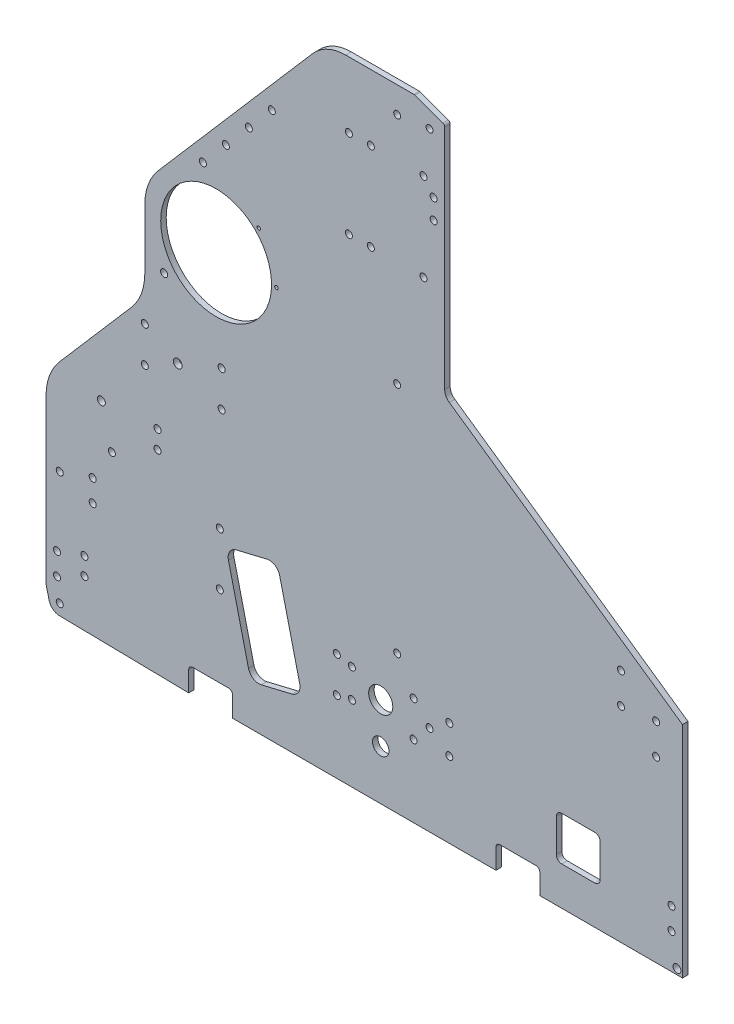
SolidWorks part; units mm, degrees
ref_plane "Front Plane" through (0, 0, 0) normal (0, 0, 1) x (1, 0, 0)
ref_plane "Top Plane" through (0, 0, 0) normal (0, 1, 0) x (1, 0, 0)
ref_plane "Right Plane" through (0, 0, 0) normal (1, 0, 0) x (0, 0, -1)
sketch "Sketch1" plane through (0, 0, 0) normal (0, 0, 1) x (1, 0, 0)
  line L0 (82.55, -20.32) -> (82.55, -6.35)
  line L2 (0, 0) -> (0, 157.48)
  line L4 (368.3, -20.32) -> (368.3, 106.68)
  line L5 (82.55, -6.35) -> (107.95, -6.35)
  line L6 (107.95, -6.35) -> (107.95, -20.32)
  line L7 (107.95, -20.32) -> (260.35, -20.32)
  line L8 (260.35, -20.32) -> (260.35, -6.35)
  line L9 (260.35, -6.35) -> (285.75, -6.35)
  line L10 (285.75, -6.35) -> (285.75, -20.32)
  line L11 (285.75, -20.32) -> (368.3, -20.32)
  line L12 (361.95, 12.7) -> (368.3, 12.7) construction
  line L13 (0, 0) -> (6.35, 0) construction
  line L14 (0.1896, -7.8901) -> (1.7771, -14.2401)
  line L15 (7.8295, -19.0491) -> (82.55, -20.32)
  line L16 (0, 0) -> (0, -6.35)
  line L17 (76.2, 141.605) -> (79.375, 141.605) construction
  line L18 (57.15, 131.2863) -> (101.6, 131.2862) construction
  line L19 (57.15, 131.2863) -> (57.15, 151.9238) construction
  line L20 (101.6, 131.2862) -> (101.6, 151.9237) construction
  line L21 (57.15, 151.9238) -> (101.6, 151.9237) construction
  line L22 (57.15, 131.2863) -> (101.6, 151.9237) construction
  line L23 (101.6, 131.2862) -> (57.15, 151.9238) construction
  line L25 (203.2, 59.805) -> (203.2, 194.805) construction
  line L26 (203.2, 194.805) -> (203.2, 329.805) construction
  line L27 (355.6, 332.105) -> (330.2, 332.105) construction
  line L28 (330.2, 332.105) -> (330.2, 217.805) construction
  line L29 (330.2, 217.805) -> (355.6, 217.805) construction
  line L30 (355.6, 217.805) -> (355.6, 332.105) construction
  line L31 (203.2, 344.805) -> (203.2, 194.805) construction
  line L32 (50.8, 332.105) -> (76.2, 332.105) construction
  line L33 (76.2, 332.105) -> (76.2, 217.805) construction
  line L34 (50.8, 217.805) -> (50.8, 332.105) construction
  line L35 (76.2, 217.805) -> (50.8, 217.805) construction
  line L36 (213.2, 344.805) -> (230.6638, 338.455)
  line L37 (203.2, 344.805) -> (161.925, 344.805)
  line L38 (203.2, 344.805) -> (213.2, 344.805)
  line L39 (348.5362, 344.805) -> (413.4623, 344.805)
  line L40 (348.5362, 344.805) -> (230.6638, 344.805) construction
  line L42 (161.925, 344.805) -> (0, 157.48)
  line L44 (230.6638, 338.455) -> (230.6638, 202.565)
  line L45 (230.6638, 202.565) -> (368.3, 106.68)
  line L46 (213.2, 344.805) -> (-141.0713, 344.805) construction
  circle A0 centre (6.35, 0) radius 2.032
  circle A1 centre (6.35, 12.7) radius 2.032
  circle A2 centre (361.95, 0) radius 2.032
  circle A3 centre (361.95, 12.7) radius 2.032
  arc A5 (1.7771, -14.2401) -> (7.8295, -19.0491) centre (7.9375, -12.7) ccw
  circle A6 centre (7.9375, -12.7) radius 2.032
  arc A7 (0, -6.35) -> (0.1896, -7.8901) centre (6.35, -6.35) ccw
  circle A8 centre (38.1, 78.105) radius 2.032
  circle A9 centre (76.2, 141.605) radius 2.54
  circle A10 centre (101.6, 131.2862) radius 2.032
  circle A11 centre (101.6, 151.9237) radius 2.032
  circle A12 centre (57.15, 151.9238) radius 2.032
  circle A13 centre (57.15, 131.2863) radius 2.032
  circle A15 centre (203.2, 59.805) radius 2
  circle A16 centre (203.2, 194.805) radius 2
  circle A17 centre (203.2, 329.805) radius 2
  circle A18 centre (63.5, 313.055) radius 2.032
  circle A20 centre (355.6, 332.105) radius 2.032
  circle A21 centre (330.2, 332.105) radius 2.032
  circle A22 centre (355.6, 217.805) radius 2.032
  circle A23 centre (330.2, 217.805) radius 2.032
  circle A24 centre (50.8, 332.105) radius 2.032
  circle A25 centre (76.2, 332.105) radius 2.032
  circle A26 centre (50.8, 217.805) radius 2.032
  circle A27 centre (76.2, 217.805) radius 2.032
  circle A28 centre (221.9319, 332.105) radius 2
  circle A29 centre (224.3138, 298.831) radius 2.032
  circle A30 centre (353.06, 100.7351) radius 2.032
  circle A31 centre (332.74, 115.9751) radius 2.032
  circle A32 centre (332.74, 98.1951) radius 2.032
  circle A33 centre (353.06, 82.9551) radius 2.032
  circle A34 centre (117.3562, 280.4276) radius 2.032
  circle A35 centre (104.0678, 265.0548) radius 2.032
  circle A36 centre (90.7795, 249.682) radius 2.032
  circle A38 centre (130.6445, 295.8004) radius 2.032
  circle A39 centre (68.326, 182.9237) radius 2.032
  circle A40 centre (224.3138, 287.401) radius 2.032
  point P82 (203.2, 344.805)
  point P83 (221.9319, 341.63)
  point P90 (368.3, 62.484)
  dimension "D6" = 4.064
  dimension "D10" = 6.35
  dimension "D11" = 4.064
  dimension "D17" = 38.1
  dimension "D27" = 4
  dimension "D31" = 4.064
  dimension "D32" = 41.275
  dimension "D36" = 4.064
  dimension "D47" = 39.624
  dimension "D48" = 4.064
  dimension "D25" = 5.08
  dimension "D26" = 4.064
  dimension "D52" = 4.064
  dimension "D65" = 4.064
  dimension "D2" = 127
  dimension "D3" = 13.97
  dimension "D4" = 25.4
  dimension "D5" = 152.4
  dimension "D7" = 12.7
  dimension "D8" = 6.35
  dimension "D9" = 20.32
  dimension "D12" = 12.7
  dimension "D13" = 1.5875
  dimension "D14" = 82.55
  dimension "D15" = 368.3
  dimension "D16" = 6.35
  dimension "D18" = 98.425
  dimension "D19" = 38.1
  dimension "D20" = 63.5
  dimension "D21" = 3.175
  dimension "D22" = 270
  dimension "D23" = 20.6375
  dimension "D24" = 44.45
  dimension "D28" = 135
  dimension "D29" = 12.7
  dimension "D30" = 15
  dimension "D33" = 63.5
  dimension "D34" = 27.4638
  dimension "D35" = 12.7
  dimension "D37" = 114.3
  dimension "D38" = 25.4
  dimension "D39" = 12.7
  dimension "D40" = 157.48
  dimension "D41" = 142.24
  dimension "D42" = 365.125
  dimension "D43" = 10
  dimension "D44" = 6.35
  dimension "D45" = 31.75
  dimension "D46" = 6.35
  dimension "D49" = 6.35
  dimension "D50" = 203.2
  dimension "D51" = 15.24
  dimension "D53" = 17.78
  dimension "D54" = 17.78
  dimension "D55" = 20.32
  dimension "D56" = 15.24
  dimension "D57" = 92.202
  dimension "D58" = 8.382
  dimension "D59" = 20.32
  dimension "D60" = 20.32
  dimension "D61" = 8.382
  dimension "D62" = 20.32
  dimension "D63" = 8.382
  dimension "D64" = 8.382
  dimension "D66" = 35.052
  dimension "D67" = 68.326
  dimension "D68" = 11.43
extrude "Boss-Extrude1" add sketch "Sketch1" along normal blind 3.175 contours L16 A7 L14 A5 L15 L2 A0 A1 A6 region at (171.3489, 119.5243, 0)
fillet "Fillet1" radius 2.286 4 edges at (285.75, -6.35, 1.5875) (107.95, -6.35, 1.5875) (260.35, -6.35, 1.5875) (82.55, -6.35, 1.5875)
fillet "Fillet2" radius 6.35 1 edges at (230.6638, 202.565, 1.5875)
sketch "Sketch2" plane through (0, 0, 0) normal (0, 0, -1) x (-1, 0, 0)
  circle A0 centre (-100.5528, 71.086) radius 2.032 construction
  circle A1 centre (-100.5528, 40.606) radius 2.032 construction
  circle A2 centre (-22.225, 18.2025) radius 2.032 construction
  circle A3 centre (-22.225, 8.0425) radius 2.032 construction
  circle A4 centre (-100.5528, 71.086) radius 2.032
  circle A5 centre (-100.5528, 40.606) radius 2.032
  circle A6 centre (-22.225, 18.2025) radius 2.032
  circle A7 centre (-22.225, 8.0425) radius 2.032
extrude "Cut-Extrude1" cut sketch "Sketch2" against normal through all
fillet "Fillet3" radius 1.5875 2 edges at (230.6638, 338.455, 1.5875) (213.2, 344.805, 1.5875)
sketch "Sketch3" plane through (0, 0, 3.175) normal (0, 0, 1) x (1, 0, 0)
  line L0 (132.9524, 63.2646) -> (132.7215, 64.2281) construction
  line L1 (128.3814, 66.8897) -> (110.6828, 62.6472) construction
  line L2 (114.5132, 58.4237) -> (126.8822, 61.3887) construction
  line L3 (108.0212, 58.3071) -> (108.2522, 57.3436) construction
  line L4 (131.2006, 57.703) -> (140.0164, 20.9265) construction
  line L5 (144.0993, 16.7636) -> (132.9524, 63.2646) construction
  line L6 (108.2522, 57.3436) -> (119.3991, 10.8426) construction
  line L7 (121.1509, 16.4042) -> (112.3351, 53.1807) construction
  line L8 (119.3991, 10.8426) -> (119.6301, 9.8791) construction
  line L9 (144.3303, 15.8001) -> (144.0993, 16.7636) construction
  line L10 (137.8383, 15.6835) -> (125.4694, 12.7185) construction
  line L11 (123.9701, 7.2175) -> (141.6687, 11.4601) construction
  line L12 (132.9524, 63.2646) -> (132.7215, 64.2281)
  line L13 (128.3814, 66.8897) -> (110.6828, 62.6472)
  line L14 (114.5132, 58.4237) -> (126.8822, 61.3887)
  line L15 (108.0212, 58.3071) -> (108.2522, 57.3436)
  line L16 (131.2006, 57.703) -> (140.0164, 20.9265)
  line L17 (144.0993, 16.7636) -> (132.9524, 63.2646)
  line L18 (108.2522, 57.3436) -> (119.3991, 10.8426)
  line L19 (121.1509, 16.4042) -> (112.3351, 53.1807)
  line L20 (119.3991, 10.8426) -> (119.6301, 9.8791)
  line L21 (144.3303, 15.8001) -> (144.0993, 16.7636)
  line L22 (137.8383, 15.6835) -> (125.4694, 12.7185)
  line L23 (123.9701, 7.2175) -> (141.6687, 11.4601)
  line L24 (127.7894, 69.3598) -> (110.0908, 65.1172)
  line L25 (105.5512, 57.715) -> (105.7822, 56.7515)
  line L26 (105.7822, 56.7515) -> (116.9291, 10.2505)
  line L27 (116.9291, 10.2505) -> (117.16, 9.287)
  line L28 (124.5622, 4.7475) -> (142.2608, 8.99)
  line L29 (146.8003, 16.3922) -> (146.5694, 17.3557)
  line L30 (146.5694, 17.3557) -> (135.4225, 63.8567)
  line L31 (135.4225, 63.8567) -> (135.1915, 64.8202)
  line L32 (14.605, -0.1369) -> (103.7278, 32.3011) construction
  line L33 (14.605, -0.1369) -> (103.7278, 32.3011)
  line L34 (0, -6.35) -> (0, 157.48) construction
  line L35 (-39.6666, 74.7152) -> (103.7278, 126.9065) construction
  line L36 (26.9875, 46.9531) -> (26.9875, 59.6531) construction
  line L37 (107.95, -20.32) -> (260.35, -20.32) construction
  line L38 (64.5259, 92.5258) -> (64.5259, 102.9405) construction
  arc A0 (132.7215, 64.2281) -> (128.6308, 66.9403) centre (129.2206, 63.3889) ccw construction
  arc A1 (110.6828, 62.6472) -> (110.4377, 62.5791) centre (111.522, 59.1463) ccw construction
  arc A2 (128.6308, 66.9403) -> (128.3814, 66.8897) centre (129.2206, 63.3889) ccw construction
  arc A3 (110.4377, 62.5791) -> (108.0212, 58.3071) centre (111.522, 59.1463) ccw construction
  arc A4 (119.6301, 9.8791) -> (123.7207, 7.1669) centre (123.1309, 10.7183) ccw construction
  arc A5 (141.9139, 11.5281) -> (144.3303, 15.8001) centre (140.8295, 14.9609) ccw construction
  arc A6 (141.6687, 11.4601) -> (141.9139, 11.5281) centre (140.8295, 14.9609) ccw construction
  arc A7 (123.7207, 7.1669) -> (123.9701, 7.2175) centre (123.1309, 10.7183) ccw construction
  arc A8 (132.7215, 64.2281) -> (128.6308, 66.9403) centre (129.2206, 63.3889) ccw
  arc A9 (110.6828, 62.6472) -> (110.4377, 62.5791) centre (111.522, 59.1463) ccw
  arc A10 (128.6308, 66.9403) -> (128.3814, 66.8897) centre (129.2206, 63.3889) ccw
  arc A11 (110.4377, 62.5791) -> (108.0212, 58.3071) centre (111.522, 59.1463) ccw
  arc A12 (119.6301, 9.8791) -> (123.7207, 7.1669) centre (123.1309, 10.7183) ccw
  arc A13 (141.9139, 11.5281) -> (144.3303, 15.8001) centre (140.8295, 14.9609) ccw
  arc A14 (141.6687, 11.4601) -> (141.9139, 11.5281) centre (140.8295, 14.9609) ccw
  arc A15 (123.7207, 7.1669) -> (123.9701, 7.2175) centre (123.1309, 10.7183) ccw
  arc A16 (110.0908, 65.1172) -> (109.6726, 65.0012) centre (111.522, 59.1463) ccw
  arc A17 (109.6726, 65.0012) -> (105.5512, 57.715) centre (111.522, 59.1463) ccw
  arc A18 (117.16, 9.287) -> (124.1369, 4.6613) centre (123.1309, 10.7183) ccw
  arc A19 (124.1369, 4.6613) -> (124.5622, 4.7475) centre (123.1309, 10.7183) ccw
  arc A20 (142.2608, 8.99) -> (142.6789, 9.1061) centre (140.8295, 14.9609) ccw
  arc A21 (142.6789, 9.1061) -> (146.8003, 16.3922) centre (140.8295, 14.9609) ccw
  arc A22 (135.1915, 64.8202) -> (128.2147, 69.446) centre (129.2206, 63.3889) ccw
  arc A23 (128.2147, 69.446) -> (127.7894, 69.3598) centre (129.2206, 63.3889) ccw
  circle A26 centre (133.35, 208.2281) radius 1.016 construction
  circle A33 centre (26.9875, 46.9531) radius 2.032
  circle A34 centre (26.9875, 59.6531) radius 2.032
  circle A35 centre (7.9375, 53.3031) radius 2.032
  circle A37 centre (32.0306, 100.8109) radius 31.75 construction
  circle A38 centre (32.0306, 100.8109) radius 2.286
  circle A39 centre (123.1207, 232.9238) radius 1.016 construction
  circle A40 centre (64.5259, 102.9405) radius 2.032
  circle A41 centre (64.5259, 92.5258) radius 2.032
  circle A42 centre (133.35, 208.2281) radius 1.016
  circle A43 centre (123.1207, 232.9238) radius 1.016
  ellipse E0 centre (124.5974, 48.8487) end of major axis (128.5376, 61.3578) minor radius 6 (131.2006, 57.703) -> (126.8822, 61.3887) ccw construction
  ellipse E1 centre (122.2349, 48.2824) end of major axis (113.0518, 57.6456) minor radius 6 (114.5132, 58.4237) -> (112.3351, 53.1807) ccw construction
  ellipse E2 centre (127.7541, 25.2585) end of major axis (131.6942, 37.7675) minor radius 6 (121.1509, 16.4042) -> (125.4694, 12.7185) ccw construction
  ellipse E3 centre (130.1166, 25.8248) end of major axis (139.2998, 16.4616) minor radius 6 (137.8383, 15.6835) -> (140.0164, 20.9265) ccw construction
  ellipse E4 centre (124.5974, 48.8487) end of major axis (120.6573, 36.3397) minor radius 6 (131.2006, 57.703) -> (126.8822, 61.3887) ccw
  ellipse E5 centre (122.2349, 48.2824) end of major axis (131.4181, 38.9192) minor radius 6 (114.5132, 58.4237) -> (112.3351, 53.1807) ccw
  ellipse E6 centre (127.7541, 25.2585) end of major axis (131.6942, 37.7675) minor radius 6 (121.1509, 16.4042) -> (125.4694, 12.7185) ccw
  ellipse E7 centre (130.1166, 25.8248) end of major axis (139.2998, 16.4616) minor radius 6 (137.8383, 15.6835) -> (140.0164, 20.9265) ccw
  point P93 (26.9875, 53.3031)
  point P115 (32.0306, 100.8109)
  dimension "D3" = 63.5
  dimension "D4" = 4.572
  dimension "D8" = 4.064
  dimension "D2" = 88.9
  dimension "D5" = 7.9375
  dimension "D6" = 19.05
  dimension "D7" = 73.6231
  dimension "D9" = 12.7
  dimension "D10" = 10.4147
  dimension "D11" = 37.5384
  dimension "D12" = 45.5727
  dimension "D1" = 2.54
extrude "Cut-Extrude2" cut sketch "Sketch3" against normal through all contours A22 A23 L24 A16 A17 L25 L26 L27 A18 A19 L28 A20 A21 L29 L30 L31 A15 A12 L20 L18 L15 A11 A9 L13 A10 A8 L12 L17 L21 A13 A14 L23 | A12 A15 L23 A14 A13 L21 L17 L12 A8 A10 L13 A9 A11 L15 L18 L20 E7 L22 E6 L19 E5 L14 E4 L16 | L22 E7 L16 E4 L14 E5 L19 E6 | A38 | A41 | A40 | A35 | A34 | A33 | A43 | A42 region at (137.844, 39.8506, 3.175) region at (126.1758, 37.0536, 3.175) region at (128.1544, 68.6507, 3.175) region at (32.0306, 100.8109, 3.175) region at (64.5259, 102.9405, 3.175) region at (64.5259, 92.5258, 3.175)
sketch "Sketch4" plane through (0, 0, 3.175) normal (0, 0, 1) x (1, 0, 0)
  line L0 (57.15, 151.9238) -> (101.6, 151.9237) construction
  line L1 (168.275, 21.4312) -> (212.725, 21.4312) construction
  line L2 (168.275, 21.4312) -> (168.275, 42.0687) construction
  line L3 (168.275, 42.0687) -> (212.725, 42.0687) construction
  line L4 (212.725, 21.4312) -> (212.725, 42.0687) construction
  line L5 (168.275, 21.4312) -> (212.725, 42.0687) construction
  line L6 (168.275, 42.0687) -> (212.725, 21.4312) construction
  line L7 (57.15, 131.2863) -> (57.15, 151.9238) construction
  line L8 (107.95, -20.32) -> (260.35, -20.32) construction
  line L9 (193.675, 31.75) -> (177.005, 31.75) construction
  line L10 (190.5, 31.75) -> (193.675, 31.75) construction
  line L11 (6.35, 12.7) -> (361.95, 12.7) construction
  line L12 (107.95, -6.35) -> (107.95, -20.32) construction
  line L13 (193.675, 31.75) -> (220.6625, 31.75) construction
  line L14 (177.005, 23.4569) -> (177.005, 40.0431) construction
  line L15 (213.2, 44.805) -> (193.2, 44.805) construction
  line L16 (213.2, 44.805) -> (213.2, 344.805) construction
  line L17 (213.2, 344.805) -> (193.2, 344.805) construction
  line L18 (193.2, 44.805) -> (193.2, 344.805) construction
  line L19 (213.2, 44.805) -> (193.2, 344.805) construction
  line L20 (213.2, 344.805) -> (193.2, 44.805) construction
  line L21 (226.9319, 332.105) -> (226.9319, 31.75) construction
  line L22 (237.33, 40.0431) -> (233.3612, 40.0431) construction
  line L23 (237.33, 23.4569) -> (233.3612, 23.4569) construction
  circle A0 centre (168.275, 42.0687) radius 2.032
  circle A1 centre (212.725, 42.0687) radius 2.032
  circle A2 centre (212.725, 21.4312) radius 2.032
  circle A3 centre (168.275, 21.4312) radius 2.032
  circle A4 centre (193.675, 31.75) radius 6.985
  circle A7 centre (220.6625, 31.75) radius 14.2875 construction
  circle A8 centre (193.675, 31.75) radius 12.7 construction
  circle A9 centre (177.005, 40.0431) radius 2.032
  circle A10 centre (177.005, 23.4569) radius 2.032
  circle A11 centre (237.33, 40.0431) radius 2.032 construction
  circle A12 centre (237.33, 23.4569) radius 2.032 construction
  circle A13 centre (193.675, 8.4667) radius 4.7625
  circle A14 centre (221.9319, 31.75) radius 2.032
  circle A15 centre (221.9319, 31.75) radius 5 construction
  circle A16 centre (221.9319, 332.105) radius 5 construction
  circle A17 centre (233.3612, 23.4569) radius 2.032
  circle A18 centre (233.3612, 40.0431) radius 2.032
  point P0 (190.5, 31.75)
  point P26 (203.2, 194.805)
  point P38 (177.005, 31.75)
  dimension "D1" = 4.064
  dimension "D4" = 13.97
  dimension "D7" = 9.525
  dimension "D10" = 25.4
  dimension "D11" = 28.575
  dimension "D16" = 10
  dimension "D17" = 4.064
  dimension "D18" = 10
  dimension "D2" = 52.07
  dimension "D3" = 3.175
  dimension "D5" = 82.55
  dimension "D6" = 26.9875
  dimension "D8" = 20
  dimension "D9" = 300
  dimension "D12" = 16.67
  dimension "D13" = 16.5862
  dimension "D14" = 60.325
  dimension "D15" = 23.2833
  dimension "D19" = 3.9688
extrude "Cut-Extrude3" cut sketch "Sketch4" against normal through all
sketch "Sketch5" plane through (0, 0, -187.325) normal (0, 0, -1) x (-1, 0, 0)
  line L0 (-57.15, 223.5947) -> (-57.15, 165.3337)
  line L1 (-161.925, 344.805) -> (-52.7201, 218.4699) construction
  line L2 (-57.15, 165.3337) -> (0, 99.219)
  line L3 (0, -6.35) -> (0, 157.48) construction
  line L4 (-50.4199, 215.8089) -> (0, 157.48) construction
  line L5 (-50.4199, 215.8089) -> (0, 157.48) construction
  line L6 (-57.15, 223.5947) -> (0, 157.48)
  line L7 (0, 157.48) -> (0, 99.219)
  circle A0 centre (-98.425, 208.2281) radius 32.0675
  circle A1 centre (-365.125, -17.145) radius 2.286 construction
  circle A2 centre (-365.125, -17.145) radius 2.286
  dimension "D3" = 64.135
  dimension "D1" = 38.1
  dimension "D2" = 57.15
  dimension "D4" = 41.275
  dimension "D5" = 41.275
extrude "Cut-Extrude5" cut sketch "Sketch5" against normal through all contours A0 | L7 L6 L0 L2 | A2 region at (28.575, 161.4068, -187.325) region at (98.425, 208.2281, -187.325)
fillet "Fillet4" radius 31.75 3 edges at (0, 99.219, 1.5875) (57.15, 165.3337, 1.5875) (57.15, 223.5947, 1.5875)
sketch "Sketch6" plane through (0, 0, 3.175) normal (0, 0, 1) x (1, 0, 0)
  line L0 (285.75, -20.32) -> (368.3, -20.32) construction
  line L1 (298.45, 27.305) -> (317.5, 27.305)
  line L2 (295.275, 24.13) -> (295.275, 5.08)
  line L3 (298.45, 1.905) -> (317.5, 1.905)
  line L4 (320.675, 24.13) -> (320.675, 5.08)
  line L5 (295.275, 27.305) -> (320.675, 1.905) construction
  line L6 (295.275, 1.905) -> (320.675, 27.305) construction
  line L7 (368.3, -20.32) -> (368.3, 106.68) construction
  arc A0 (295.275, 5.08) -> (298.45, 1.905) centre (298.45, 5.08) ccw
  arc A1 (317.5, 1.905) -> (320.675, 5.08) centre (317.5, 5.08) ccw
  arc A2 (317.5, 27.305) -> (320.675, 24.13) centre (317.5, 24.13) cw
  arc A3 (298.45, 27.305) -> (295.275, 24.13) centre (298.45, 24.13) ccw
  point P0 (307.975, 14.605)
  dimension "D2" = 3.175
  dimension "D1" = 25.4
  dimension "D3" = 22.225
  dimension "D4" = 47.625
extrude "Cut-Extrude6" cut sketch "Sketch6" against normal through all
fillet "Fillet5" radius 25.4 1 edges at (161.925, 344.805, 1.5875)
sketch "Sketch8" plane through (0, 0, 0) normal (0, 0, -1) x (-1, 0, 0)
  circle A0 centre (-187.96, 306.705) radius 2.032 construction
  arc A1 (-176.3652, 304.9998) -> (-176.3652, 308.4102) centre (-175.26, 306.705) ccw construction
  arc A2 (-219.0586, 304.7695) -> (-219.0586, 308.6405) centre (-218.44, 306.705) ccw construction
  circle A3 centre (-205.74, 306.705) radius 2.032 construction
  arc A4 (-219.0586, 253.9695) -> (-219.0586, 257.8405) centre (-218.44, 255.905) ccw construction
  circle A5 centre (-205.74, 255.905) radius 2.032 construction
  circle A6 centre (-187.96, 255.905) radius 2.032 construction
  arc A7 (-176.3652, 254.1998) -> (-176.3652, 257.6102) centre (-175.26, 255.905) ccw construction
  circle A8 centre (-187.96, 306.705) radius 2.032
  arc A9 (-176.3652, 304.9998) -> (-176.3652, 308.4102) centre (-175.26, 306.705) ccw
  arc A10 (-219.0586, 304.7695) -> (-219.0586, 308.6405) centre (-218.44, 306.705) ccw
  circle A11 centre (-205.74, 306.705) radius 2.032
  arc A12 (-219.0586, 253.9695) -> (-219.0586, 257.8405) centre (-218.44, 255.905) ccw
  circle A13 centre (-205.74, 255.905) radius 2.032
  circle A14 centre (-187.96, 255.905) radius 2.032
  arc A15 (-176.3652, 254.1998) -> (-176.3652, 257.6102) centre (-175.26, 255.905) ccw
  circle A16 centre (-218.44, 306.705) radius 2.032
  circle A17 centre (-175.26, 306.705) radius 2.032
  circle A18 centre (-175.26, 255.905) radius 2.032
  circle A19 centre (-218.44, 255.905) radius 2.032
  circle A20 centre (-218.44, 306.705) radius 3.9688
  circle A21 centre (-205.74, 306.705) radius 3.9687
  circle A22 centre (-175.26, 306.705) radius 3.9687
  circle A23 centre (-218.44, 255.905) radius 3.9687
  circle A24 centre (-205.74, 255.905) radius 3.9687
  circle A25 centre (-187.96, 255.905) radius 3.9688
  circle A26 centre (-175.26, 255.905) radius 3.9687
  circle A27 centre (-187.96, 306.705) radius 3.9687
  dimension "D1" = 7.9375
extrude "Cut-Extrude7" cut sketch "Sketch8" against normal through all contours A10 A16 | A9 A17 | A15 A18 | A12 A19 | A8 | A14 region at (175.26, 306.705, 0) region at (218.44, 306.705, 0) region at (218.44, 255.905, 0) region at (175.26, 255.905, 0)
